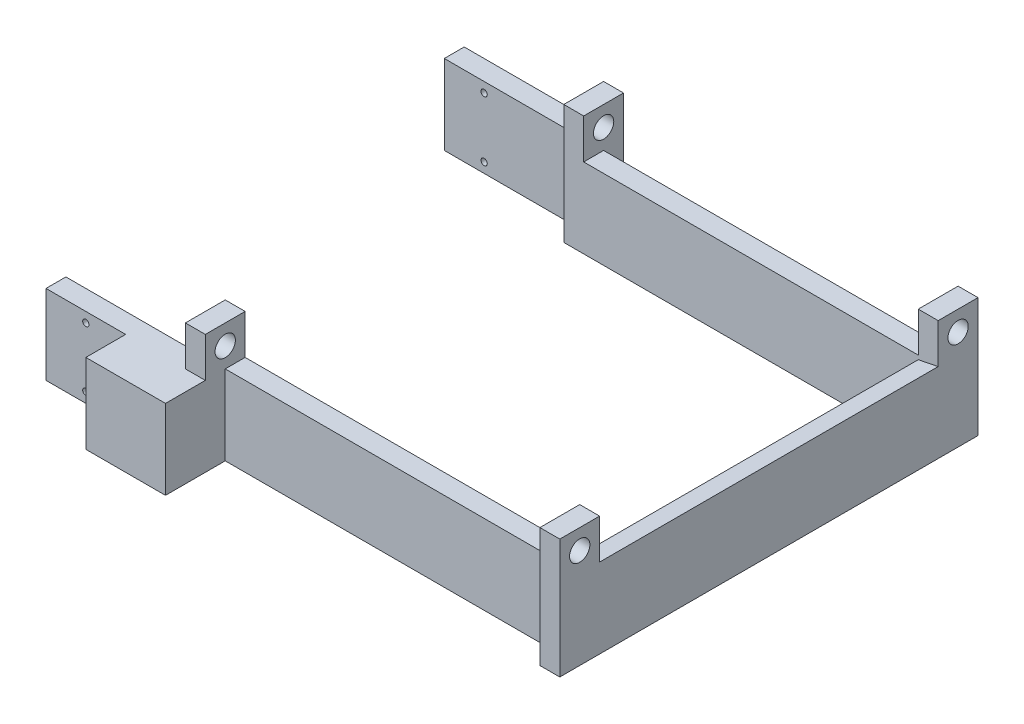
SolidWorks part; units mm, degrees
ref_plane "Front Plane" through (0, 0, 0) normal (0, 0, 1) x (1, 0, 0)
ref_plane "Top Plane" through (0, 0, 0) normal (0, 1, 0) x (1, 0, 0)
ref_plane "Right Plane" through (0, 0, 0) normal (1, 0, 0) x (0, 0, -1)
sketch "Sketch1" plane through (0, 0, 0) normal (0, 1, 0) x (1, 0, 0)
  line L0 (3.175, 114.3) -> (0, 114.3)
  line L1 (0, 0) -> (119.38, 0)
  line L2 (0, 0) -> (0, 6.35)
  line L3 (0, 120.65) -> (119.38, 120.65)
  line L4 (119.38, 0) -> (119.38, 120.65)
  line L5 (3.175, 114.3) -> (113.03, 114.3)
  line L7 (3.175, 6.35) -> (113.03, 6.35)
  line L8 (113.03, 114.3) -> (113.03, 6.35)
  line L9 (3.175, 6.35) -> (0, 6.35)
  line L10 (0, 114.3) -> (0, 120.65)
  dimension "D1" = 120.65
  dimension "D2" = 113.03
  dimension "D3" = 6.35
  dimension "D5" = 6.35
  dimension "D6" = 107.95
extrude "Boss-Extrude1" add sketch "Sketch1" along normal blind 25.4
sketch "Sketch2" plane through (0, 0, 0) normal (0, 0, 1) x (1, 0, 0)
  line L0 (119.38, 25.4) -> (113.03, 24.13)
  line L1 (113.03, 24.13) -> (113.03, 25.4)
  line L2 (0, 25.4) -> (119.38, 25.4) construction
  line L4 (113.03, 25.4) -> (119.38, 25.4)
  dimension "D2" = 1.27
extrude "Cut-Extrude1" cut sketch "Sketch2" against normal up to surface (114.3 mm away) from surface up to face at (56.515, 12.7, -114.3) starting at face at (56.515, 12.7, -6.35)
sketch "Sketch3" plane through (0, 0, 0) normal (0, 0, 1) x (1, 0, 0)
  line L0 (0, 25.4) -> (119.38, 25.4) construction
  line L1 (6.35, 25.4) -> (-44.45, 25.4)
  line L2 (6.35, 25.4) -> (6.35, 0)
  line L3 (6.35, 0) -> (-44.45, 0)
  line L4 (-44.45, 25.4) -> (-44.45, 0)
  line L5 (0, 25.4) -> (0, 0) construction
  dimension "D1" = 6.35
  dimension "D2" = 44.45
extrude "Boss-Extrude2" add sketch "Sketch3" along normal blind 6.35
extrude "Boss-Extrude3" add sketch "Sketch3<2>" against normal blind 6.35 from surface starting at face at (59.69, 12.7, -120.65)
sketch "Sketch3<2>" plane through (0, 0, 0) normal (0, 0, 1) x (1, 0, 0) same geometry as "Sketch3"
sketch "Sketch8" plane through (0, 25.4, 0) normal (0, 1, 0) x (1, 0, 0)
  line L0 (119.38, 60.325) -> (-5.0576, 60.325) construction
  line L1 (119.38, -6.35) -> (113.03, -6.35)
  line L2 (119.38, -6.35) -> (119.38, 6.35)
  line L4 (113.03, -6.35) -> (113.03, 6.35)
  line L5 (113.03, 6.35) -> (119.38, 6.35)
  line L6 (59.69, 114.3) -> (59.69, -20.9935) construction
  line L7 (0, 114.3) -> (119.38, 114.3) construction
  line L8 (119.38, 114.3) -> (119.38, 6.35) construction
  line L9 (6.35, -6.35) -> (6.35, 6.35)
  line L10 (0, 6.35) -> (6.35, 6.35)
  line L11 (0, -6.35) -> (0, 6.35)
  line L12 (0, -6.35) -> (6.35, -6.35)
  line L22 (0, 127) -> (6.35, 127)
  line L23 (0, 127) -> (0, 114.3)
  line L24 (0, 114.3) -> (6.35, 114.3)
  line L25 (6.35, 127) -> (6.35, 114.3)
  line L26 (113.03, 127) -> (113.03, 114.3)
  line L27 (119.38, 114.3) -> (113.03, 114.3)
  line L28 (119.38, 127) -> (119.38, 114.3)
  line L29 (119.38, 127) -> (113.03, 127)
  dimension "D1" = 12.7
extrude "Boss-Extrude4" add sketch "Sketch8" along normal blind 38.1 from surface starting at face at (19.5263, 0, -60.325)
sketch "Sketch9" plane through (119.38, 0, 0) normal (1, 0, 0) x (0, 0, -1)
  line L0 (-6.35, 38.1) -> (6.35, 38.1) construction
  line L3 (60.325, 36.7762) -> (60.325, 19.9574) construction
  line L4 (6.35, 38.1) -> (6.35, 0) construction
  line L5 (-6.35, 38.1) -> (-6.35, 0) construction
  circle A0 centre (0, 31.75) radius 3.2385
  circle A1 centre (120.65, 31.75) radius 3.2385
  dimension "D1" = 6.477
  dimension "D4" = 53.975
  dimension "D2" = 6.35
  dimension "D3" = 6.35
extrude "Cut-Extrude2" cut sketch "Sketch9" against normal through all both and the other way through all
sketch "Sketch10" plane through (0, 0, 6.35) normal (0, 0, 1) x (1, 0, 0)
  line L0 (0, 25.4) -> (-44.45, 25.4) construction
  line L1 (-44.45, 25.4) -> (-44.45, 0) construction
  circle A0 centre (-31.75, 22.225) radius 1
  circle A1 centre (-31.75, 3.175) radius 1
  dimension "D2" = 2
  dimension "D4" = 2
  dimension "D1" = 3.175
  dimension "D3" = 12.7
  dimension "D5" = 19.05
  dimension "D6" = 12.7
extrude "Cut-Extrude3" cut sketch "Sketch10" against normal through all
sketch "Sketch11" plane through (0, 0, 6.35) normal (0, 0, 1) x (1, 0, 0)
  line L0 (-44.45, 0) -> (6.35, 0) construction
  line L1 (6.35, 25.4) -> (-19.05, 25.4)
  line L2 (6.35, 25.4) -> (6.35, 0)
  line L3 (6.35, 0) -> (-19.05, 0)
  line L4 (-19.05, 25.4) -> (-19.05, 0)
  dimension "D1" = 25.4
extrude "Boss-Extrude5" add sketch "Sketch11" along normal blind 12.7
equation "\"tightTol\" = 0.005in"
equation "\"normTol\"= 0.01in"
equation "\"looseTol\"= 0.02in"
equation "\"D1@Sketch9\"=\"tightTol\"+0.250000in"
equation "\"D2@Sketch10\"=2mm"
equation "\"D4@Sketch10\"=2mm"
